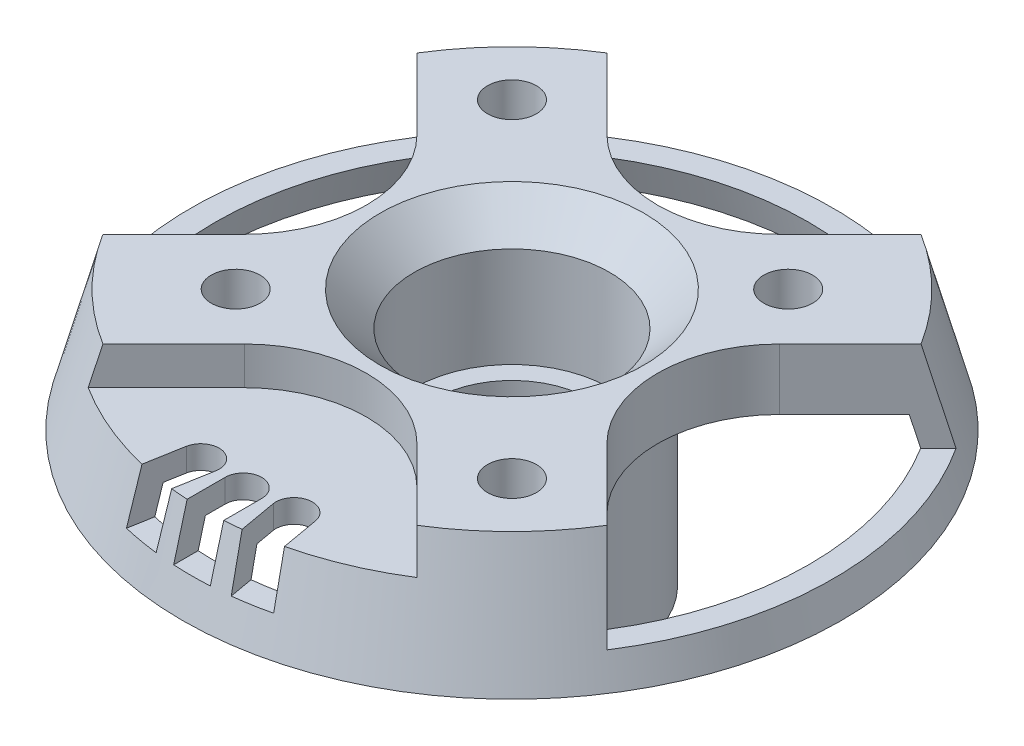
SolidWorks part; units mm, degrees
ref_plane "Front Plane" through (0, 0, 0) normal (0, 0, 1) x (1, 0, 0)
ref_plane "Top Plane" through (0, 0, 0) normal (0, 1, 0) x (1, 0, 0)
ref_plane "Right Plane" through (0, 0, 0) normal (1, 0, 0) x (0, 0, -1)
sketch "Sketch1" plane through (0, 0, 0) normal (0, 1, 0) x (1, 0, 0)
  circle A0 centre (0, 0) radius 13.5
  dimension "D1" = 27
extrude "Base size" add sketch "Sketch1" along normal blind 5
sketch "Sketch2" plane through (0, 5, 0) normal (0, 1, 0) x (1, 0, 0)
  line L0 (-9.5459, -9.5459) -> (9.5459, 9.5459) construction
  line L1 (-13.5, 0) -> (13.5, 0) construction
  line L2 (-9.5459, 9.5459) -> (9.5459, -9.5459) construction
  line L3 (0, 13.5) -> (0, -13.5) construction
  circle A0 centre (0, 0) radius 13.5 construction
  circle A1 centre (5.6569, 5.6569) radius 1
  circle A2 centre (-5.6569, -5.6569) radius 1
  circle A3 centre (-6.7175, 6.7175) radius 1
  circle A4 centre (6.7175, -6.7175) radius 1
  dimension "D2" = 2
  dimension "D1" = 45
  dimension "D3" = 16
  dimension "D4" = 19
extrude "Mounting holes" cut sketch "Sketch2" against normal up to next
sketch "Sketch3" plane through (0, 0, 0) normal (0, -1, 0) x (1, 0, 0)
  circle A0 centre (0, 0) radius 12.5
  circle A1 centre (0, 0) radius 13.5 construction
  dimension "D1" = 1
extrude "Rotor pocket" cut sketch "Sketch3" against normal blind 2.5 draft 15
chamfer "Outside chamfer" distance 5 angle 15 1 edges at (0, 5, 13.5) first distance on face at (0, 5, 13.5)
sketch "Sketch4" plane through (0, 5, 0) normal (0, 1, 0) x (1, 0, 0)
  line L0 (-8.5986, 8.5986) -> (8.5986, -8.5986) construction
  line L2 (0, 12.1603) -> (0, -12.1603) construction
  line L3 (-12.1603, 0) -> (12.1603, 0) construction
  line L4 (-8.5986, -8.5986) -> (8.5986, 8.5986) construction
  line L5 (-10.5431, 6.6541) -> (6.6541, -10.5431)
  line L6 (-6.6541, -10.5431) -> (10.5431, 6.6541)
  line L7 (-6.6541, 10.5431) -> (10.5431, -6.6541)
  line L8 (-10.5431, -6.6541) -> (6.6541, 10.5431)
  line L9 (-10.5431, 6.6541) -> (-11.2903, 7.4012)
  line L10 (-6.6541, 10.5431) -> (-7.4012, 11.2903)
  line L11 (6.6541, 10.5431) -> (7.4012, 11.2903)
  line L12 (10.5431, 6.6541) -> (11.2903, 7.4012)
  line L13 (10.5431, -6.6541) -> (11.2903, -7.4012)
  line L14 (6.6541, -10.5431) -> (7.4012, -11.2903)
  line L15 (-6.6541, -10.5431) -> (-7.4012, -11.2903)
  line L16 (-10.5431, -6.6541) -> (-11.2903, -7.4012)
  circle A0 centre (0, 0) radius 12.1603 construction
  circle A1 centre (0, 0) radius 13.5
  circle A2 centre (0, 0) radius 13.5 construction
  point P29 (0, 0)
  circle M9 centre (0, 0) radius 12.1603
  dimension "D1" = 2.75
  dimension "D2" = 2.75
extrude "Bottom pockets top" cut sketch "Sketch4" against normal blind 1.55 contours L8 L5 M9 | L9 A1 L16 L8 L5 M9 | L7 L8 M9 | L11 A1 L10 L7 L8 M9 | L6 L7 M9 | L13 A1 L12 L6 L7 M9 | L15 A1 L14 L5 L6 M9 | L6 L5 M9 region at (-12.1626, 5, 0) region at (-8.9824, 5, 0) region at (0, 5, -8.9824) region at (0, 5, -12.1626) region at (0, 5, 8.9824) region at (0, 5, 12.1626) region at (8.9824, 5, 0) region at (12.1626, 5, 0)
sketch "Sketch5" plane through (0, 3.45, 0) normal (0, 1, 0) x (1, 0, 0)
  line L0 (-11.2903, 7.4012) -> (7.4012, -11.2903)
  line L1 (-10.3204, 6.4313) -> (-3.8891, 0) construction
  line L2 (7.4012, 11.2903) -> (-11.2903, -7.4012)
  line L3 (-10.3204, -6.4313) -> (-3.8891, 0) construction
  line L4 (-7.4012, 11.2903) -> (11.2903, -7.4012)
  line L5 (-6.4313, 10.3204) -> (0, 3.8891) construction
  line L6 (-7.4012, -11.2903) -> (11.2903, 7.4012)
  line L7 (3.8891, 0) -> (10.6216, 6.7325) construction
  circle A0 centre (0, 0) radius 13.5
  circle A1 centre (0, 0) radius 13.5 construction
  line M5 (-10.6216, -6.7325) -> (-3.8891, 0)
  line M6 (-3.8891, 0) -> (-10.6216, 6.7325)
  arc M7 (-10.6216, 6.7325) -> (-10.6216, -6.7325) centre (0, 0) ccw
extrude "Bottom pockets bottom" cut sketch "Sketch5" against normal offset from surface (2.15 mm away) 1.3 contours M7 M5 M6 | L0 A0 L2 M7 | L2 A0 L4 | L4 A0 L6 region at (-11.0626, 3.45, -6.9602) region at (-9.2333, 3.45, 0) region at (0, 3.45, -9.7912) region at (9.7912, 3.45, 0) up to face at (0, 0, -12.5)
fillet "Bottom pockets fillet" radius 5 4 edges at (0, 4.225, 3.8891) (3.8891, 3.75, 0) (0, 3.75, -3.8891) (-3.8891, 3.75, 0)
sketch "Sketch6" plane through (0, 5, 0) normal (0, 1, 0) x (1, 0, 0)
  circle A0 centre (0, 0) radius 4
  dimension "D1" = 8
extrude "Cut-Extrude5" cut sketch "Sketch6" against normal up to next
chamfer "Chamfer2" distance 1.4 angle 45 1 edges at (0, 5, 4)
sketch "Sketch7" plane through (0, 2.5, 0) normal (0, -1, 0) x (1, 0, 0)
  circle A0 centre (0, 0) radius 4
  circle A1 centre (0, 0) radius 4.8
  circle A2 centre (0, 0) radius 4 construction
  dimension "D1" = 0.8
extrude "Bearing bottom" add sketch "Sketch7" along normal blind 3
sketch "Sketch8" plane through (0, -0.5, 0) normal (0, -1, 0) x (1, 0, 0)
  circle A0 centre (0, 0) radius 4.8 construction
  circle A1 centre (0, 0) radius 4.8
  circle A2 centre (0, 0) radius 3.2
  circle A3 centre (0, 0) radius 4 construction
  dimension "D1" = 0.8
extrude "Bearing separator" add sketch "Sketch8" along normal blind 1
sketch "Sketch9" plane through (0, -1.5, 0) normal (0, -1, 0) x (1, 0, 0)
  circle A0 centre (0, 0) radius 4.8 construction
  circle A1 centre (0, 0) radius 4.8
  circle A2 centre (0, 0) radius 4 construction
  circle A3 centre (0, 0) radius 4
extrude "Bearing top" add sketch "Sketch9" along normal blind 4
sketch "Sketch10" plane through (0, 3.45, 0) normal (0, 1, 0) x (1, 0, 0)
  line L0 (0, -13.5) -> (0, 13.5) construction
  line L1 (0, 0) -> (0, -11) construction
  line L2 (0, 0) -> (-1.9101, -10.8329) construction
  line L3 (-2.6439, -10.6775) -> (-3.0788, -13.1442)
  line L4 (-1.1675, -10.9379) -> (-1.6025, -13.4046)
  line L5 (-0.75, -11) -> (-0.75, -13.4792)
  line L6 (2.6439, -10.6775) -> (3.0788, -13.1442)
  line L7 (1.1675, -10.9379) -> (1.6025, -13.4046)
  line L8 (0.75, -11) -> (0.75, -13.4792)
  circle A0 centre (0, 0) radius 11
  circle A1 centre (0, 0) radius 13.5 construction
  circle A2 centre (0, -11) radius 0.75
  circle A3 centre (-1.9101, -10.8329) radius 0.75
  circle A4 centre (1.9101, -10.8329) radius 0.75
  circle A5 centre (0, 0) radius 13.5
  arc M11 (-6.7325, -10.6216) -> (6.7325, -10.6216) centre (0, 0) ccw
  dimension "D1" = 2.5
  dimension "D2" = 1.5
  dimension "D4" = 10
  dimension "D3" = 2
extrude "Cut-Extrude6" cut sketch "Sketch10" against normal offset from surface (2.05 mm away) 1.4 contours A0 A3 | L3 A3 L4 A0 | A3 L3 L4 M11 | L3 A5 L4 M11 | L5 A5 L8 M11 | A2 L5 L8 M11 | A2 A0 | A0 A2 | A4 A0 | A4 L6 A0 L7 | L6 A4 L7 M11 | L7 A5 L6 M11 region at (-1.9646, 3.45, 11.1418) region at (-1.8541, 3.45, 10.5149) region at (-2.095, 3.45, 11.8813) region at (-2.2627, 3.45, 12.8326) region at (1.9646, 3.45, 11.1418) region at (1.8541, 3.45, 10.5149) region at (0, 3.45, 10.6771) region at (0, 3.45, 11.3137) region at (2.095, 3.45, 11.8813) region at (0, 3.45, 12.0643) region at (0, 3.45, 13.0306) region at (2.2627, 3.45, 12.8326) up to face at (0, 0, -12.5)
sketch "Sketch11" plane through (0, 5, 0) normal (0, 1, 0) x (1, 0, 0)
  line L0 (6.7175, -6.7175) -> (-6.7175, 6.7175) construction
  line L1 (5.6569, 5.6569) -> (-5.6569, -5.6569) construction
  circle A0 centre (-6.7175, 6.7175) radius 1 construction
  circle A1 centre (6.7175, -6.7175) radius 1 construction
  point P8 (0, 0)
  point P9 (0, 0)
  point P10 (0, 0)
  point P13 (0, 0)
ref_axis "Center axis" through (0, 26.8978, 0) along (0, -1, 0)
